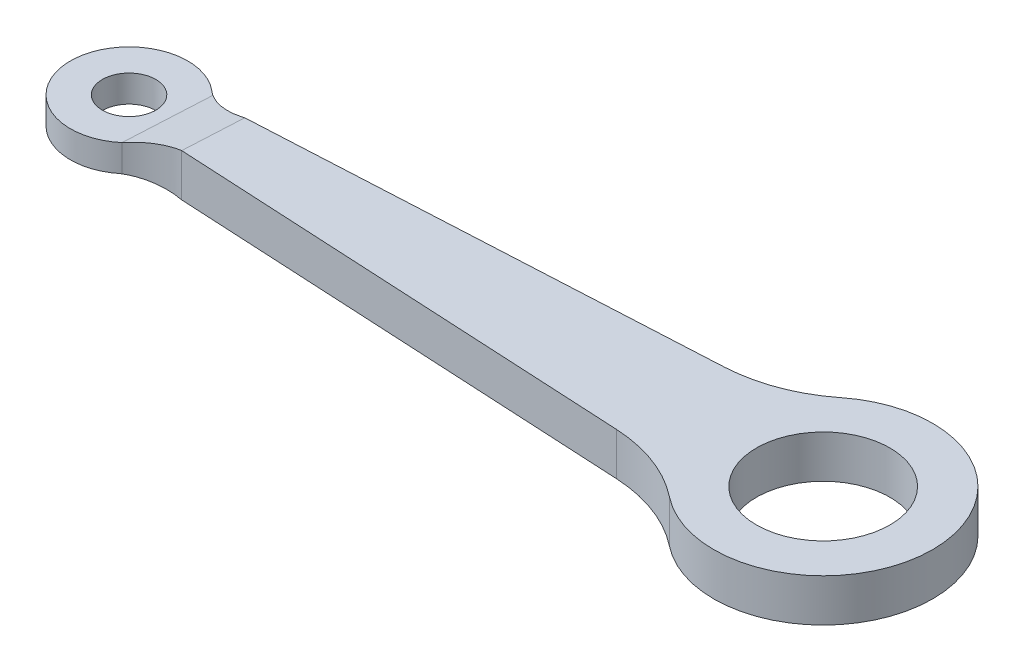
SolidWorks part; units mm, degrees
material "1060 Alloy"
ref_plane "Front Plane" through (0, 0, 0) normal (0, 0, 1) x (1, 0, 0)
ref_plane "Top Plane" through (0, 0, 0) normal (0, 1, 0) x (1, 0, 0)
ref_plane "Right Plane" through (0, 0, 0) normal (1, 0, 0) x (0, 0, -1)
sketch "Sketch1" plane through (0, 0, 0) normal (0, 1, 0) x (1, 0, 0)
  line L0 (0, 0) -> (41.275, 0) construction
  line L1 (4.9067, 1.778) -> (32.1984, 3.2083)
  line L2 (4.9067, -1.778) -> (32.1984, -3.2083)
  circle A0 centre (0, 0) radius 1.5875
  arc A1 (2.2513, 2.67) -> (2.2513, -2.67) centre (0, 0) ccw
  circle A2 centre (41.275, 0) radius 3.9688
  arc A3 (37.2418, -5.1086) -> (37.2418, 5.1086) centre (41.275, 0) ccw
  arc A4 (32.1984, 3.2083) -> (37.2418, 5.1086) centre (31.7331, 12.0861) ccw
  arc A5 (32.1984, -3.2083) -> (37.2418, -5.1086) centre (31.7331, -12.0861) cw
  arc A6 (2.2513, 2.67) -> (4.9067, 1.778) centre (4.7073, 5.5828) ccw
  arc A7 (2.2513, -2.67) -> (4.9067, -1.778) centre (4.7073, -5.5828) cw
  dimension "D1" = 3.175
  dimension "D2" = 7.9375
  dimension "D3" = 2.54
  dimension "D4" = 1.905
  dimension "D8" = 8.89
  dimension "D9" = 8.89
  dimension "D6" = 3.81
  dimension "D10" = 3.81
  dimension "D5" = 3
  dimension "D7" = 41.275
  dimension "D11" = 1.778
  dimension "D12" = 1.778
  dimension "D13" = 3
extrude "Boss-Extrude1" add sketch "Sketch1" along normal blind 1.27 and the other way blind 1.27
sketch "Sketch2" plane through (-0.0795, 0, 1.5167) normal (-0.0523, 0, 0.9986) x (0.9986, 0, 0.0523)
  line L0 (-3.4925, 0.8001) -> (2.388, 0.8001)
  line L2 (-3.4925, 0) -> (47.7272, 0) construction
  line L3 (-3.4925, 1.27) -> (-3.4925, -1.27) construction
  line L4 (47.7272, -1.27) -> (47.7272, 1.27) construction
  line L5 (-3.4925, 1.27) -> (-3.4925, -1.27) construction
  line L6 (2.388, -1.27) -> (2.388, 1.27) construction
  line L7 (2.388, 0.8001) -> (4.9931, 1.27)
  line L8 (-3.4925, 0.8001) -> (-4.8654, 1.8564)
  line L9 (-4.8654, 1.8564) -> (4.9931, 1.8564)
  line L10 (4.9931, 1.8564) -> (4.9931, 1.27)
  dimension "D1" = 0.8001
extrude "Cut-Extrude1" cut sketch "Sketch2" against normal through all both and the other way through all
sketch "Sketch3" plane through (-0.0795, 0, 1.5167) normal (-0.0523, 0, 0.9986) x (0.9986, 0, 0.0523)
  line L0 (4.9931, -1.27) -> (2.3495, -0.8039)
  line L1 (2.3495, -0.8039) -> (-3.4925, -0.8039)
  line L2 (-3.4925, 0.8001) -> (-3.4925, -1.27) construction
  line L7 (4.9931, -1.27) -> (4.9931, -2.2028)
  line L8 (4.9931, -2.2028) -> (-4.0943, -2.2028)
  line L9 (-4.0943, -2.2028) -> (-3.4925, -0.8039)
  dimension "D1" = 170
  dimension "D2" = 5.842
extrude "Cut-Extrude2" cut sketch "Sketch3" against normal through all both and the other way through all
